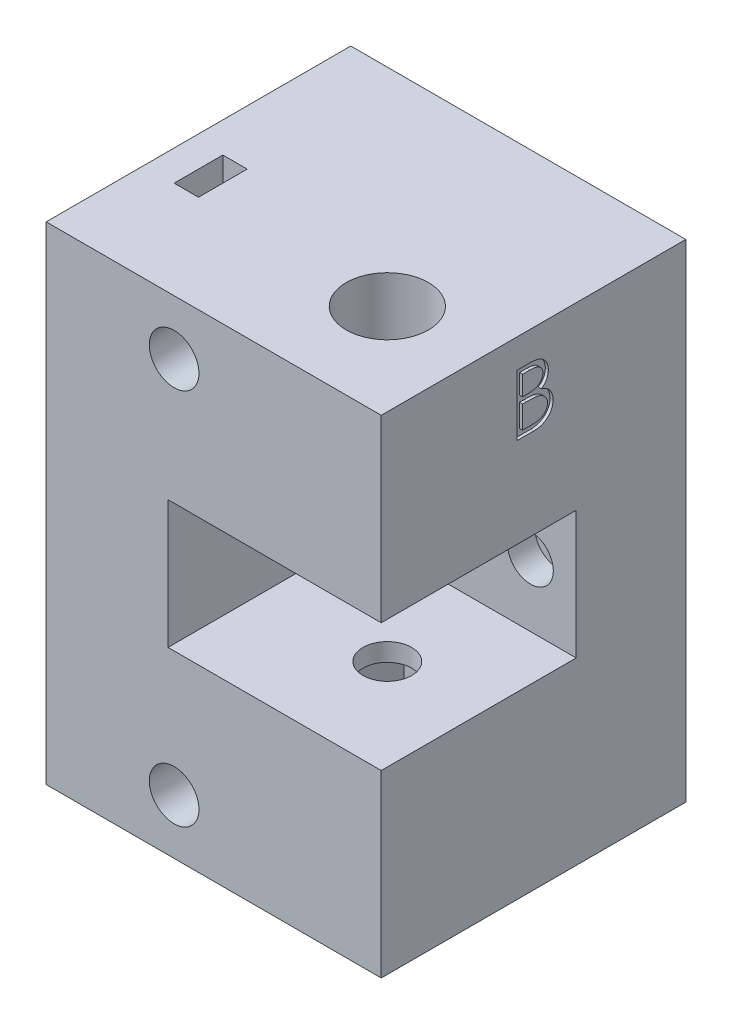
SolidWorks part; units mm, degrees
ref_plane "Front Plane" through (0, 0, 0) normal (0, 0, 1) x (1, 0, 0)
ref_plane "Top Plane" through (0, 0, 0) normal (0, 1, 0) x (1, 0, 0)
ref_plane "Right Plane" through (0, 0, 0) normal (1, 0, 0) x (0, 0, -1)
sketch "Sketch2" plane through (0, 0, 0) normal (0, 0, 1) x (1, 0, 0)
  line L1 (0, 0) -> (55, 0)
  line L2 (0, 0) -> (0, 80)
  line L3 (0, 80) -> (55, 80)
  line L4 (55, 0) -> (55, 80)
  dimension "D1" = 80
  dimension "D2" = 55
extrude "Boss-Extrude1" add sketch "Sketch2" along normal blind 50
sketch "Sketch4" plane through (0, 80, 0) normal (0, 1, 0) x (1, 0, 0)
  line L0 (0, -50) -> (42, -50) construction
  line L1 (55, -50) -> (0, -50) construction
  line L2 (21, -50) -> (21, -36.8261) construction
  circle A0 centre (40, -34) radius 4
  dimension "D3" = 8
  dimension "D1" = 42
  dimension "D2" = 19
  dimension "D4" = 16
extrude "Cut-Extrude1" cut sketch "Sketch4" against normal through all
sketch "Sketch5" plane through (0, 0, 50) normal (0, 0, 1) x (1, 0, 0)
  line L0 (0, 40) -> (42, 40) construction
  line L1 (0, 80) -> (0, 0) construction
  line L2 (21, 40) -> (21, 47.2178) construction
  line L3 (55, 80) -> (0, 80) construction
  line L4 (0, 0) -> (55, 0) construction
  circle A0 centre (21, 71) radius 4.075
  circle A1 centre (21, 9) radius 4.075
  dimension "D2" = 8.15
  dimension "D1" = 42
  dimension "D3" = 9
  dimension "D4" = 9
extrude "Cut-Extrude2" cut sketch "Sketch5" against normal blind 8.03
sketch "Sketch6" plane through (0, 0, 50) normal (0, 0, 1) x (1, 0, 0)
  line L0 (55, 0) -> (55, 80) construction
  line L1 (55, 29.5) -> (20, 29.5)
  line L2 (55, 29.5) -> (55, 50.5)
  line L3 (55, 50.5) -> (20, 50.5)
  line L4 (20, 29.5) -> (20, 50.5)
  line L5 (0, 40) -> (18.5522, 40) construction
  line L6 (0, 80) -> (0, 0) construction
  point P10 (20, 40)
  dimension "D1" = 21
  dimension "D2" = 35
extrude "Cut-Extrude3" cut sketch "Sketch6" against normal blind 32
sketch "Sketch10" plane through (0, 80, 0) normal (0, 1, 0) x (1, 0, 0)
  circle A0 centre (40, -34) radius 6.75
  dimension "D1" = 13.5
extrude "Cut-Extrude5" cut sketch "Sketch10" against normal offset from surface (26.55 mm away) 2.95 up to face at (37.5, 50.5, 34)
sketch "Sketch11" plane through (0, 0, 0) normal (0, -1, 0) x (1, 0, 0)
  line L1 (47.5633, 34) -> (43.7816, 40.55)
  line L2 (43.7816, 40.55) -> (36.2184, 40.55)
  line L3 (36.2184, 40.55) -> (32.4367, 34)
  line L4 (32.4367, 34) -> (36.2184, 27.45)
  line L5 (36.2184, 27.45) -> (43.7816, 27.45)
  line L6 (43.7816, 27.45) -> (47.5633, 34)
  circle A0 centre (40, 34) radius 6.55 construction
  dimension "D1" = 13.1
extrude "Cut-Extrude6" cut sketch "Sketch11" against normal offset from surface (26.55 mm away) 2.95 up to face at (37.5, 29.5, 34)
ref_plane "Plane1" through (35, 0, 0) normal (1, 0, 0) x (0, 0, -1)
ref_plane "Plane2" through (0, 0, 30) normal (0, 0, 1) x (1, 0, 0)
sketch "Sketch12" plane through (0, 0, 0) normal (0, -1, 0) x (1, 0, 0)
  line L0 (0, 0) -> (55, 0) construction
  circle A0 centre (12.5, 7.5) radius 2
  circle A1 centre (12.5, 22.5) radius 2
  dimension "D2" = 4
  dimension "D1" = 12.5
  dimension "D3" = 15
  dimension "D4" = 7.5
extrude "Cut-Extrude7" cut sketch "Sketch12" against normal blind 5
sketch "Sketch13" plane through (0, 0, 18) normal (0, 0, 1) x (1, 0, 0)
  line L0 (20, 40) -> (39.8047, 40) construction
  line L1 (20, 50.5) -> (20, 29.5) construction
  line L2 (55, 29.5) -> (55, 50.5) construction
  circle A0 centre (27.5, 40) radius 3.75
  circle A1 centre (47.5, 40) radius 3.75
  circle A2 centre (27.5, 40) radius 2.1
  circle A3 centre (47.5, 40) radius 2.1
  dimension "D1" = 7.5
  dimension "D2" = 20
  dimension "D4" = 4.2
  dimension "D3" = 7.5
extrude "Cut-Extrude8" cut sketch "Sketch13" against normal through all contours A3 | A2
extrude "Cut-Extrude9" cut sketch "Sketch13<3>" against normal blind 4.5 contours A1 | A0
sketch "Sketch13<3>" plane through (0, 0, 18) normal (0, 0, 1) x (1, 0, 0) same geometry as "Sketch13"
sketch "Sketch14" plane through (0, 0, 0) normal (-1, 0, 0) x (0, 0, 1)
  line L0 (50, 80) -> (0, 80) construction
  circle A0 centre (30, 72) radius 2.25
  dimension "D3" = 4.5
  dimension "D1" = 8
  dimension "D2" = 30
extrude "Cut-Extrude10" cut sketch "Sketch14" against normal blind 10
sketch "Sketch15" plane through (0, 80, 0) normal (0, 1, 0) x (1, 0, 0)
  line L0 (0, -50) -> (0, 0) construction
  line L1 (9, -34) -> (5, -34)
  line L2 (9, -34) -> (9, -26)
  line L3 (9, -26) -> (5, -26)
  line L4 (5, -34) -> (5, -26)
  point P4 (5, -30)
  dimension "D1" = 8
  dimension "D2" = 30
  dimension "D3" = 5
  dimension "D4" = 4
extrude "Cut-Extrude11" cut sketch "Sketch15" against normal blind 13
sketch "Sketch16" plane through (55, 0, 0) normal (1, 0, 0) x (0, 0, -1)
  line L0 (-50, 65.25) -> (0, 65.25) construction
  line L1 (-50, 50.5) -> (-50, 80) construction
  line L2 (0, 0) -> (0, 80) construction
  text T0 "B" font "Century Gothic" height 10
extrude "Cut-Extrude12" cut sketch "Sketch16" against normal blind 0.5
